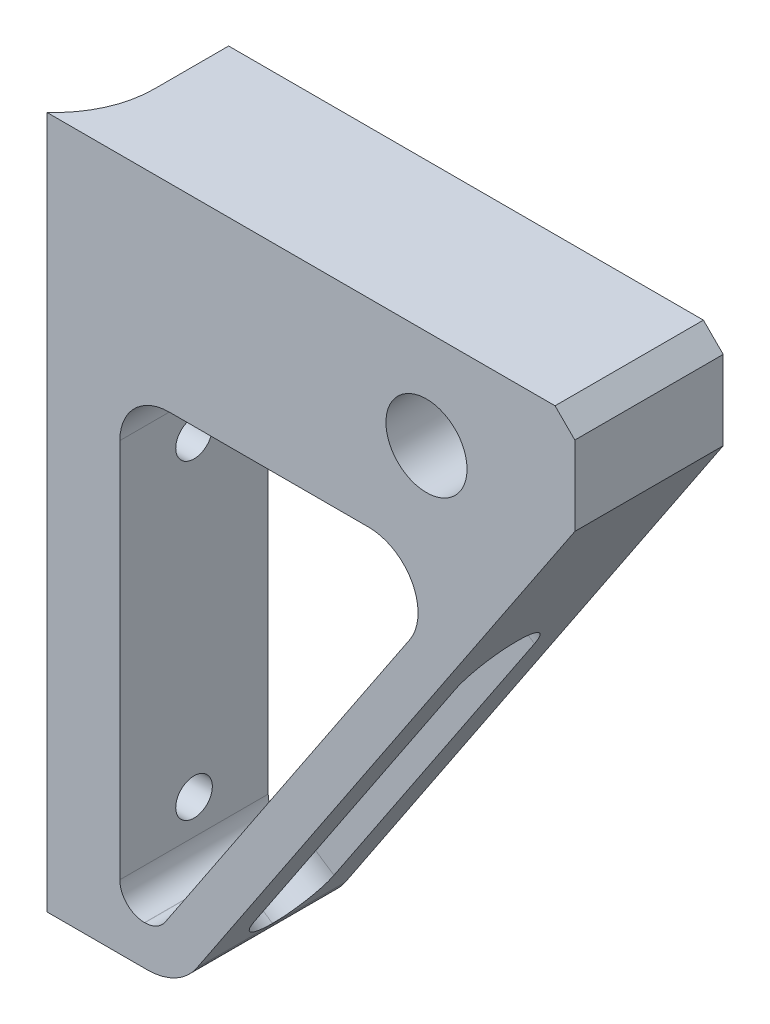
SolidWorks part; units mm, degrees
material "PET"
ref_plane "Přední rovina" through (0, 0, 0) normal (0, 0, 1) x (1, 0, 0)
ref_plane "Horní rovina" through (0, 0, 0) normal (0, 1, 0) x (1, 0, 0)
ref_plane "Pravá rovina" through (0, 0, 0) normal (1, 0, 0) x (0, 0, -1)
sketch "Skica1" plane through (0, 0, 0) normal (0, 0, 1) x (1, 0, 0)
  line L0 (0, 0) -> (0, 70)
  line L1 (0, 70) -> (50, 70)
  line L2 (50, 70) -> (50, 60)
  line L3 (50, 60) -> (10, 0)
  line L4 (10, 0) -> (0, 0)
  dimension "D1" = 10
  dimension "D2" = 10
  dimension "D3" = 50
  dimension "D4" = 70
extrude "Přidat vysunutím1" add sketch "Skica1" along normal blind 15
sketch "Skica3" plane through (0, 0, 15) normal (0, 0, 1) x (1, 0, 0)
  line L0 (-7.4486, 60) -> (62.0284, 60) construction
  line L1 (50, 70) -> (0, 70) construction
  line L2 (50, 60) -> (50, 70) construction
  circle A0 centre (35, 60) radius 4.1
  circle A1 centre (11, 60) radius 4 construction
  dimension "D2" = 8.2
  dimension "D4" = 8
  dimension "D1" = 10
  dimension "D3" = 15
  dimension "D5" = 24
extrude "Odebrat vysunutím1" cut sketch "Skica3" against normal through all
sketch "Skica4" plane through (0, 0, 0) normal (0, 0, -1) x (-1, 0, 0)
  line L0 (-35, 60) -> (-11, 60) construction
  circle A0 centre (-11, 60) radius 4.05
  dimension "D1" = 8.1
  dimension "D2" = 24
extrude "Odebrat vysunutím2" cut sketch "Skica4" against normal blind 10
sketch "Skica5" plane through (0, 0, 0) normal (0, 0, -1) x (-1, 0, 0)
  line L2 (-29.15, 49.95) -> (-9, 49.95)
  line L7 (-4, 44.95) -> (-4, 6.5)
  line L8 (-6.5213, 4) -> (-6.5, 4)
  line L9 (-8.6014, 5.1132) -> (-33.3103, 42.1765)
  line L12 (-10, 0) -> (-50, 60) construction
  line L13 (-38.5316, 50.0085) -> (-4, 50.0085) construction
  line L14 (-38.4223, 49.95) -> (-4.0585, 49.95) construction
  line L15 (-7.828, 4.0585) -> (-38.4223, 49.95) construction
  line L16 (-7.828, 4.0585) -> (-4.0585, 4.0585) construction
  line L17 (-4.0585, 49.95) -> (-4.0585, 4.0585) construction
  line L18 (0, 70) -> (0, 0) construction
  line L19 (0, 0) -> (-10, 0) construction
  line L20 (-4, 50.0085) -> (-4, 4) construction
  line L21 (-7.8593, 4) -> (-4, 4) construction
  line L22 (-7.8593, 4) -> (-38.5316, 50.0085) construction
  arc A0 (-4, 6.5) -> (-6.5, 4) centre (-6.5, 6.5) cw
  arc A1 (-6.5213, 4) -> (-8.6014, 5.1132) centre (-6.5213, 6.5) cw
  arc A2 (-9, 49.95) -> (-4, 44.95) centre (-9, 44.95) cw
  arc A3 (-33.3103, 42.1765) -> (-29.15, 49.95) centre (-29.15, 44.95) cw
  circle A8 centre (-11, 60) radius 4.05 construction
  point P18 (-5, 0)
  dimension "D1" = 6
  dimension "D5" = 2.5
  dimension "D6" = 5
  dimension "D2" = 4
  dimension "D3" = 4
  dimension "D4" = 4
extrude "Odebrat vysunutím3" cut sketch "Skica5" against normal through all
sketch "Skica6" plane through (0, 70, 0) normal (0, 1, 0) x (1, 0, 0)
  line L0 (50, -7.5) -> (-10, -7.5) construction
  line L1 (50, -15) -> (50, 0) construction
  line L2 (50, 0) -> (0, 0) construction
  line L3 (0, -15) -> (0, 0) construction
  line L4 (3.4529, 0) -> (3.4529, -15)
  line L5 (50, -15) -> (0, -15) construction
  line L6 (3.4529, -15) -> (-3.3856, -15)
  line L7 (3.4529, 0) -> (-3.3856, 0)
  arc A0 (-3.3856, -15) -> (-3.3856, 0) centre (-10, -7.5) ccw
  dimension "D1" = 20
  dimension "D2" = 10
extrude "Přidat vysunutím2" add sketch "Skica6" against normal up to surface (70 mm away) up to face at (5, 0, 7.5)
sketch "Skica7" plane through (0, 70, 0) normal (0, 1, 0) x (1, 0, 0)
  line L1 (-3.3856, 0) -> (0, 0)
  line L2 (-3.3856, 0) -> (-3.3856, -7.5)
  line L3 (-3.3856, -7.5) -> (0, -7.5)
  line L4 (0, 0) -> (0, -7.5)
  line L5 (-3.3856, 0) -> (0, -7.5) construction
  line L6 (-3.3856, -7.5) -> (0, 0) construction
  arc A0 (-3.3856, -15) -> (-3.3856, 0) centre (-10, -7.5) ccw construction
  point P4 (-1.6928, -3.75)
extrude "Odebrat vysunutím5" cut sketch "Skica7" against normal blind 10 contours L2 L3 L4 L1
sketch "Skica9" plane through (3.5949, -2.3966, 0) normal (-0.8321, 0.5547, 0) x (0, 0, 1)
  line L0 (7.5, 85.9785) -> (7.5, -1.4275) construction
  line L1 (15, 85.9785) -> (0, 85.9785) construction
  line L3 (3.5, 53.5702) -> (11.5, 53.5702)
  line L4 (3.5, 53.5702) -> (3.5, 9.0257)
  line L5 (3.5, 9.0257) -> (11.5, 9.0257)
  line L6 (11.5, 53.5702) -> (11.5, 9.0257)
  line L7 (3.5, 53.5702) -> (11.5, 9.0257) construction
  line L8 (3.5, 9.0257) -> (11.5, 53.5702) construction
  line L9 (15, 53.5702) -> (15, 9.0257) construction
  line L12 (15, 53.5702) -> (0, 53.5702) construction
  line L13 (15, 9.0257) -> (0, 9.0257) construction
  point P8 (7.5, 31.2979)
  dimension "D1" = 3.5
extrude "Odebrat vysunutím6" cut sketch "Skica9" against normal through all
fillet "Zaoblit2" radius 4 4 edges at (10.2655, 4.0038, 11.5) (10.2655, 4.0038, 3.5) (34.9744, 41.0671, 3.5) (34.9744, 41.0671, 11.5)
sketch "Skica10" plane through (4, 0, 0) normal (1, 0, 0) x (0, 0, -1)
  line L0 (-7.5, 0) -> (-7.5, 71.0053) construction
  line L1 (-15, 0) -> (0, 0) construction
  line L2 (-15, 44.95) -> (0, 44.95) construction
  circle A0 centre (-7.5, 10) radius 1.85
  circle A1 centre (-7.5, 41.45) radius 1.85
  dimension "D1" = 3.7
  dimension "D2" = 3.7
  dimension "D3" = 10
  dimension "D4" = 3.5
extrude "Odebrat vysunutím7" cut sketch "Skica10" against normal through all
fillet "Zaoblit7" radius 6 1 edges at (10, 0, 7.5)
chamfer "Zkosení1" distance 2 angle 45 1 edges at (50, 70, 7.5)
